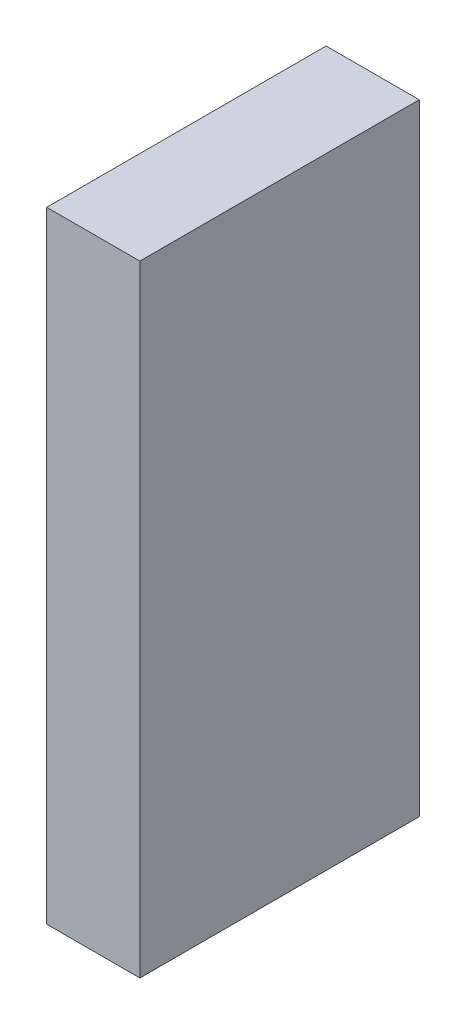
SolidWorks part; units mm, degrees
ref_plane "Front Plane" through (0, 0, 0) normal (0, 0, 1) x (1, 0, 0)
ref_plane "Top Plane" through (0, 0, 0) normal (0, 1, 0) x (1, 0, 0)
ref_plane "Right Plane" through (0, 0, 0) normal (1, 0, 0) x (0, 0, -1)
sketch "Sketch1" plane through (0, 0, 0) normal (0, 1, 0) x (1, 0, 0)
  line L1 (-15, 45) -> (15, 45)
  line L2 (-15, 45) -> (-15, -45)
  line L3 (-15, -45) -> (15, -45)
  line L4 (15, 45) -> (15, -45)
  line L5 (-15, 45) -> (15, -45) construction
  line L6 (-15, -45) -> (15, 45) construction
  point P0 (0, 0)
  dimension "D1" = 30
  dimension "D2" = 90
extrude "Boss-Extrude1" add sketch "Sketch1" along normal mid plane 200
